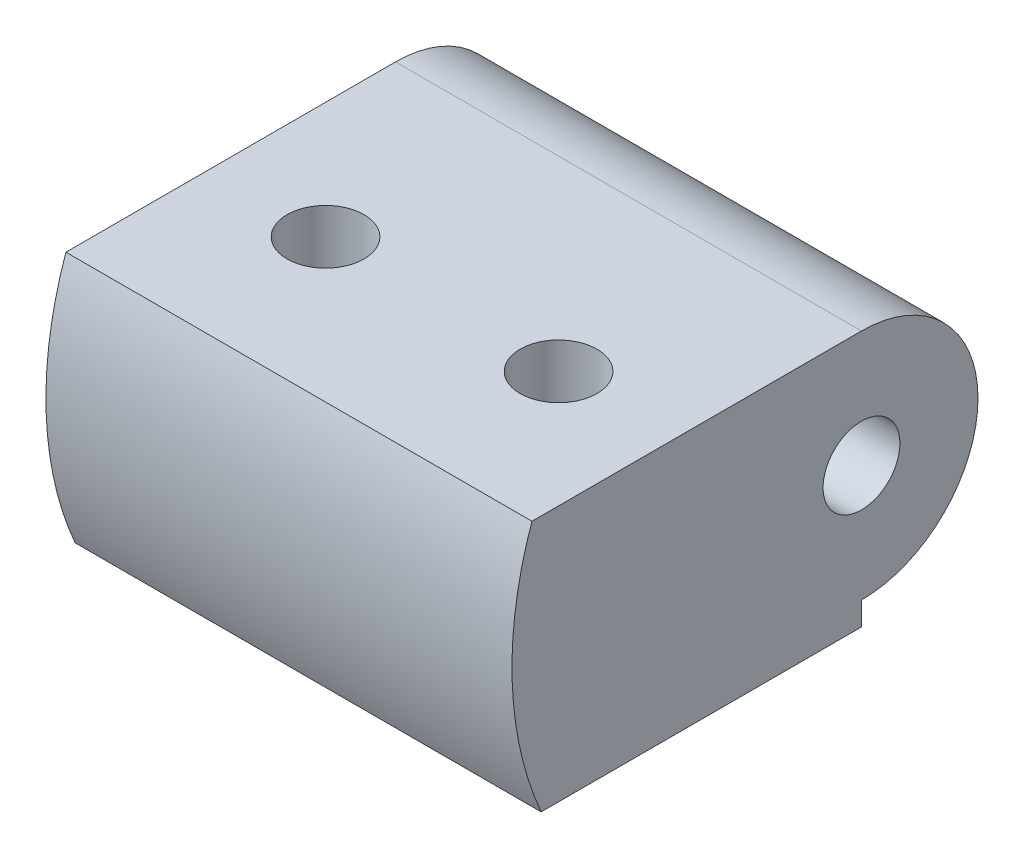
SolidWorks part; units mm, degrees
ref_plane "Front Plane" through (0, 0, 0) normal (0, 0, 1) x (1, 0, 0)
ref_plane "Top Plane" through (0, 0, 0) normal (0, 1, 0) x (1, 0, 0)
ref_plane "Right Plane" through (0, 0, 0) normal (1, 0, 0) x (0, 0, -1)
sketch "Sketch1" plane through (0, 0, 0) normal (0, 1, 0) x (1, 0, 0)
  line L1 (-10, -10) -> (10, -10)
  line L2 (-10, -10) -> (-10, 10)
  line L3 (-10, 10) -> (10, 10)
  line L4 (10, -10) -> (10, 10)
  line L5 (-10, -10) -> (10, 10) construction
  line L6 (-10, 10) -> (10, -10) construction
  point P0 (0, 0)
  dimension "D1" = 20
  dimension "D2" = 20
extrude "Boss-Extrude1" add sketch "Sketch1" along normal blind 10
fillet "Fillet1" radius 5 2 edges at (0, 0, -10) (0, 10, -10)
hole_wizard "M4x0.7 Tapped Hole1" positions "Sketch2" profile "Sketch4" tap size "M4x0.7" standard "ANSI Metric" end condition up to next
sketch "Sketch2" plane through (10, 0, 0) normal (1, 0, 0) x (0, 0, -1)
  line L0 (5, 10) -> (5, 0)
  point P6 (5, 5)
sketch "Sketch4" plane through (10, 5, -5) normal (0, 1, 0) x (0, 0, -1)
  line L0 (0, 0) -> (0, 20)
  line L1 (0, 20) -> (1.65, 20)
  line L2 (1.65, 20) -> (1.65, 0)
  line L5 (1.65, 0) -> (0, 0)
  line L11 (0, -6.35) -> (0, 107.95) construction
  dimension "Thru Tap Drill Dia." = 3.3
  dimension "Thru Tap Drill Depth" = 20
cosmetic thread "Hole Thread1" parameters "D2"=4
sketch "Sketch14" plane through (0, 0, 0) normal (0, -1, 0) x (1, 0, 0)
  line L1 (-10, 10) -> (10, 10)
  line L2 (-10, 10) -> (-10, -5)
  line L3 (-10, -5) -> (10, -5)
  line L4 (10, 10) -> (10, -5)
extrude "Boss-Extrude4" add sketch "Sketch14" along normal blind 1
hole_wizard "M4x0.7 Tapped Hole2" positions "Sketch7" profile "Sketch8" tap size "M4x0.7" standard "ANSI Metric" end condition up to next
sketch "Sketch7" plane through (0, 10, 0) normal (0, 1, 0) x (1, 0, 0)
  line L0 (-5, -3) -> (5, -3)
  point P0 (-5, -3)
  point P1 (5, -3)
  point P4 (0, -3)
  dimension "D1" = 10
  dimension "D2" = 7
sketch "Sketch8" plane through (-5, 10, 3) normal (1, 0, 0) x (0, 0, 1)
  line L0 (0, 0) -> (0, 11)
  line L1 (0, 11) -> (1.65, 11)
  line L2 (1.65, 11) -> (1.65, 0)
  line L5 (1.65, 0) -> (0, 0)
  line L11 (0, -6.35) -> (0, 107.95) construction
  dimension "Thru Tap Drill Dia." = 3.3
  dimension "Thru Tap Drill Depth" = 11
cosmetic thread "Hole Thread4" parameters "D2"=4
cosmetic thread "Hole Thread5" parameters "D2"=4
sketch "Sketch9" plane through (10, 0, 0) normal (1, 0, 0) x (0, 0, -1)
  line L1 (20, 0) -> (-10, 0)
  line L2 (20, 0) -> (20, 10)
  line L3 (20, 10) -> (-10, 10)
  line L4 (-10, 0) -> (-10, 10)
  line L5 (20, 0) -> (-10, 10) construction
  line L6 (20, 10) -> (-10, 0) construction
  line L7 (-10, 0) -> (5, 0)
  line L8 (-10, 0) -> (-10, -1)
  line L9 (-10, -1) -> (5, -1)
  line L10 (5, 0) -> (5, -1)
  circle A0 centre (5, 5) radius 15
extrude "Cut-Extrude1" cut sketch "Sketch9" against normal through all
